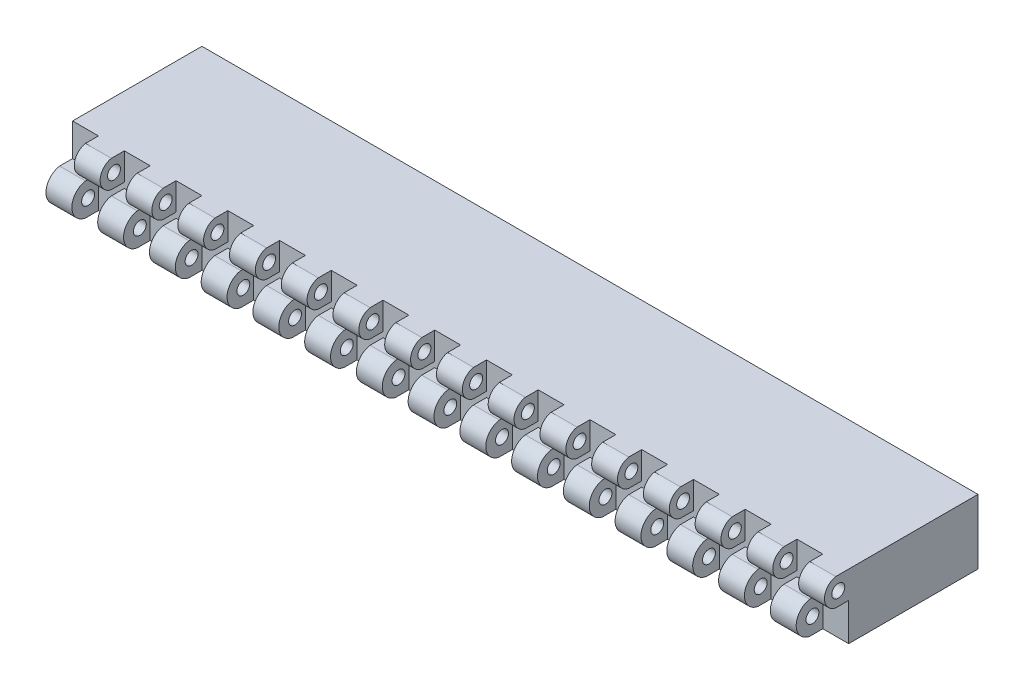
SolidWorks part; units mm, degrees
ref_plane "Front Plane" through (0, 0, 0) normal (0, 0, 1) x (1, 0, 0)
ref_plane "Top Plane" through (0, 0, 0) normal (0, 1, 0) x (1, 0, 0)
ref_plane "Right Plane" through (0, 0, 0) normal (1, 0, 0) x (0, 0, -1)
sketch "Sketch1" plane through (0, 0, 0) normal (1, 0, 0) x (0, 0, -1)
  line L1 (-25, 12.5) -> (25, 12.5)
  line L2 (-25, 12.5) -> (-25, -12.5)
  line L3 (-25, -12.5) -> (25, -12.5)
  line L4 (25, 12.5) -> (25, -12.5)
  line L5 (-25, 12.5) -> (25, -12.5) construction
  line L6 (-25, -12.5) -> (25, 12.5) construction
  point P0 (0, 0)
  dimension "D1" = 25
  dimension "D2" = 50
extrude "Boss-Extrude1" add sketch "Sketch1" along normal mid plane 300
sketch "Sketch2" plane through (150, 0, 0) normal (1, 0, 0) x (0, 0, -1)
  line L1 (-25, -12.5) -> (-25, 2) construction
  line L2 (-25, 2) -> (-25, 12.5)
  line L3 (-25, 2) -> (-30, 2)
  line L4 (-25, 12.5) -> (-30, 12.5)
  line L5 (25, 12.5) -> (-25, 12.5) construction
  arc A1 (-30, 12.5) -> (-30, 2) centre (-29, 7.25) ccw
  circle A2 centre (-29, 7.25) radius 2.5
  point P7 (-25, 7.25)
  dimension "D3" = 5
  dimension "D1" = 10.5
  dimension "D2" = 5
  dimension "D4" = 4
extrude "Boss-Extrude2" add sketch "Sketch2" against normal blind 10
pattern_linear "LPattern1" count 15 spacing 20 along (-1, 0, 0) of "Boss-Extrude2"
sketch "Sketch3" plane through (-150, 0, 0) normal (-1, 0, 0) x (0, 0, 1)
  line L0 (25, -12.5) -> (25, 0)
  line L1 (25, 12.5) -> (25, -12.5) construction
  line L2 (25, -12.5) -> (-25, -12.5) construction
  line L3 (25, -0.091) -> (30, -0.091)
  line L4 (25, -12.5) -> (30, -12.5)
  arc A1 (30, -12.5) -> (30, -0.091) centre (29, -6.2955) ccw
  circle A2 centre (29, -6.2955) radius 2.5
  point P7 (25, -6.25)
  dimension "D2" = 4
  dimension "D1" = 5
extrude "Boss-Extrude3" add sketch "Sketch3" against normal blind 10 contours L4 A1 L3 L0 A2 region at (-150, -6.2955, 25.1612)
pattern_linear "LPattern2" count 15 spacing 20 along (1, 0, 0) of "Boss-Extrude3"
sketch "Sketch4" plane through (0, 0, -25) normal (0, 0, -1) x (-1, 0, 0)
  circle A0 centre (0, 0) radius 8
  dimension "D1" = 16
extrude "Cut-Extrude1" cut sketch "Sketch4" against normal blind 30
